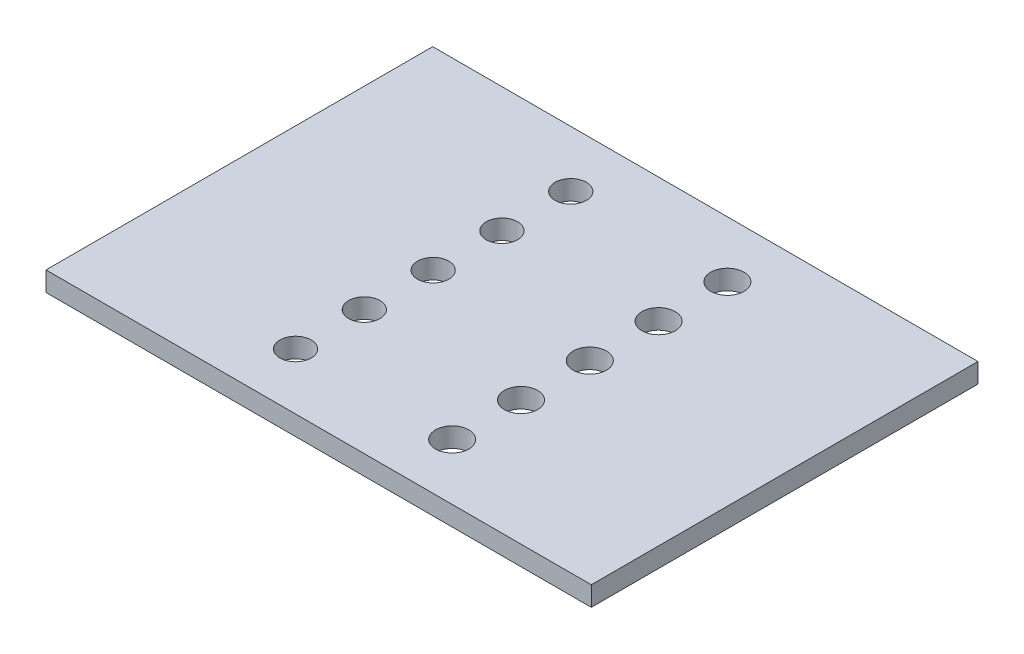
SolidWorks part; units mm, degrees
ref_plane "Front Plane" through (0, 0, 0) normal (0, 0, 1) x (1, 0, 0)
ref_plane "Top Plane" through (0, 0, 0) normal (0, 1, 0) x (1, 0, 0)
ref_plane "Right Plane" through (0, 0, 0) normal (1, 0, 0) x (0, 0, -1)
sketch "Sketch1" plane through (0, 0, 0) normal (0, 1, 0) x (1, 0, 0)
  line L1 (27.85, 19.75) -> (-27.85, 19.75)
  line L2 (27.85, 19.75) -> (27.85, -19.75)
  line L3 (27.85, -19.75) -> (-27.85, -19.75)
  line L4 (-27.85, 19.75) -> (-27.85, -19.75)
  line L5 (27.85, 19.75) -> (-27.85, -19.75) construction
  line L6 (27.85, -19.75) -> (-27.85, 19.75) construction
  point P0 (0, 0)
  dimension "D1" = 55.7
  dimension "D2" = 39.5
extrude "Boss-Extrude1" add sketch "Sketch1" along normal blind 2 contours L1 L4 L3 L2
sketch "Sketch2" plane through (0, 2, 0) normal (0, 1, 0) x (1, 0, 0)
  line L0 (27.85, 19.75) -> (27.85, -19.75) construction
  line L4 (0, 0) -> (0, 7) construction
  line L11 (-8, 0) -> (-8, 14) construction
  line L12 (-8, 0) -> (8, 14) construction
  line L13 (8, 0) -> (-8, 14) construction
  line L14 (-8, 0) -> (-8, 14) construction
  line L15 (-8, 0) -> (8, 0) construction
  line L16 (8, 0) -> (8, 14) construction
  line L17 (-8, 14) -> (8, 14) construction
  line L18 (-8, 0) -> (8, 14) construction
  line L19 (8, 0) -> (-8, 14) construction
  circle A5 centre (-8, 0) radius 1.6 construction
  circle A6 centre (-8, 14) radius 1.6
  circle A7 centre (8, 14) radius 1.7
  circle A8 centre (8, 0) radius 1.7 construction
  circle A9 centre (7.9727, 7.0001) radius 1.7
  circle A10 centre (-8.0273, 7.0001) radius 1.6
  circle A11 centre (7.9454, 0.0001) radius 1.7
  circle A12 centre (-8.0546, 0.0001) radius 1.6
  circle A13 centre (7.9181, -6.9998) radius 1.7
  circle A14 centre (-8.0819, -6.9998) radius 1.6
  circle A15 centre (7.8908, -13.9998) radius 1.7
  circle A16 centre (-8.1092, -13.9998) radius 1.6
  point P8 (0, 7)
  dimension "D3" = 5
  dimension "D2" = 3.2
  dimension "D1" = 7
  dimension "D5" = 14
  dimension "D6" = 16
extrude "Cut-Extrude2" cut sketch "Sketch2" against normal through all
